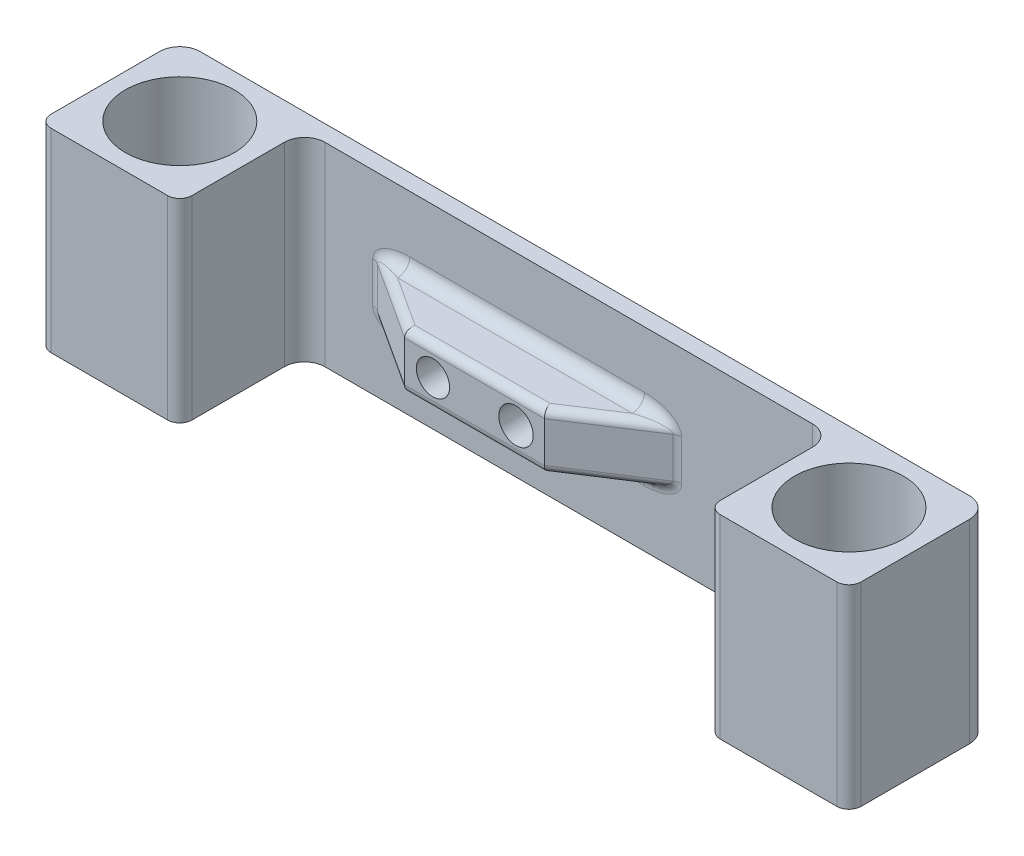
SolidWorks part; units mm, degrees
ref_plane "Front Plane" through (0, 0, 0) normal (0, 0, 1) x (1, 0, 0)
ref_plane "Top Plane" through (0, 0, 0) normal (0, 1, 0) x (1, 0, 0)
ref_plane "Right Plane" through (0, 0, 0) normal (1, 0, 0) x (0, 0, -1)
sketch "Sketch1" plane through (0, 0, 0) normal (0, 1, 0) x (1, 0, 0)
  line L1 (-17.4, 17.4) -> (17.4, 17.4)
  line L2 (-17.4, 13.4) -> (-17.4, -17.4)
  line L3 (-17.4, -17.4) -> (17.4, -17.4)
  line L4 (17.4, 17.4) -> (17.4, -17.4)
  line L5 (0, -17.4) -> (0, 17.4) construction
  line L6 (-17.4, 0) -> (17.4, 0) construction
  line L7 (-17.4, 17.4) -> (-82.6, 17.4)
  line L9 (-17.4, 13.4) -> (-82.6, 13.4)
  line L10 (-82.6, 17.4) -> (-82.6, 13.4)
  circle A0 centre (0, 0) radius 13.45
  dimension "D1" = 26.9
  dimension "D2" = 34.8
  dimension "D3" = 34.8
  dimension "D4" = 65.2
  dimension "D5" = 4
extrude "Boss-Extrude2" add sketch "Sketch1" along normal blind 48
mirror "Mirror2" about plane through (-82.6, 48, -17.4) normal (1, 0, 0) of "Boss-Extrude2"
sketch "Sketch7" plane through (0, 0, -13.4) normal (0, 0, 1) x (1, 0, 0)
  line L0 (-147.8, 24) -> (-17.4, 24) construction
  line L1 (-147.8, 48) -> (-147.8, 0) construction
  line L2 (-17.4, 48) -> (-17.4, 0) construction
  line L3 (-82.6, 48) -> (-82.6, 0) construction
  line L4 (-147.8, 48) -> (-17.4, 48) construction
  line L5 (-147.8, 0) -> (-17.4, 0) construction
  line L6 (-103.1, 24) -> (-82.6, 24) construction
  line L8 (-110.1, 17) -> (-75.6, 17)
  line L9 (-110.1, 17) -> (-110.1, 31)
  line L10 (-110.1, 31) -> (-75.6, 31)
  line L11 (-75.6, 17) -> (-75.6, 31)
  line L12 (-92.85, 31) -> (-92.85, 17) construction
  line L13 (-110.1, 24) -> (-75.6, 24) construction
  circle A0 centre (-82.6, 24) radius 4.25
  circle A2 centre (-103.1, 24) radius 4.1
  point P15 (-92.85, 24)
  dimension "D1" = 8.5
  dimension "D3" = 8.2
  dimension "D5" = 20.5
  dimension "D2" = 14
  dimension "D4" = 34.5
extrude "Boss-Extrude3" add sketch "Sketch7" along normal blind 13
fillet "Fillet1" radius 3 4 edges at (17.4, 24, 17.4) (-17.4, 24, 17.4) (-182.6, 24, 17.4) (-147.8, 24, 17.4)
fillet "Fillet2" radius 5 4 edges at (17.4, 24, -17.4) (-17.4, 24, -13.4) (-182.6, 24, -17.4) (-147.8, 24, -13.4)
sketch "Sketch8" plane through (0, 31, 0) normal (0, 1, 0) x (1, 0, 0)
  line L0 (-75.6, 0.4) -> (-55.6, 13.4)
  line L1 (-142.8, 13.4) -> (-22.4, 13.4) construction
  line L2 (-110.1, 0.4) -> (-130.1, 13.4)
  line L3 (-55.6, 13.4) -> (-75.6, 13.4)
  line L4 (-130.1, 13.4) -> (-110.1, 13.4)
  line L5 (-75.6, 0.4) -> (-75.6, 13.4)
  line L6 (-110.1, 0.4) -> (-110.1, 13.4)
  dimension "D1" = 20
  dimension "D2" = 20
extrude "Boss-Extrude4" add sketch "Sketch8" against normal blind 14
fillet "Fillet3" radius 2 6 edges at (-65.6, 17, -6.9) (-65.6, 31, -6.9) (-92.85, 31, -0.4) (-92.85, 17, -0.4) (-120.1, 17, -6.9) (-120.1, 31, -6.9)
fillet "Fillet4" radius 3 8 edges at (-56.6749, 17.5858, -13.4) (-92.85, 17, -13.4) (-129.0251, 17.5858, -13.4) (-130.1, 24, -13.4) (-129.0251, 30.4142, -13.4) (-92.85, 31, -13.4) (-56.6749, 30.4142, -13.4) (-55.6, 24, -13.4)
